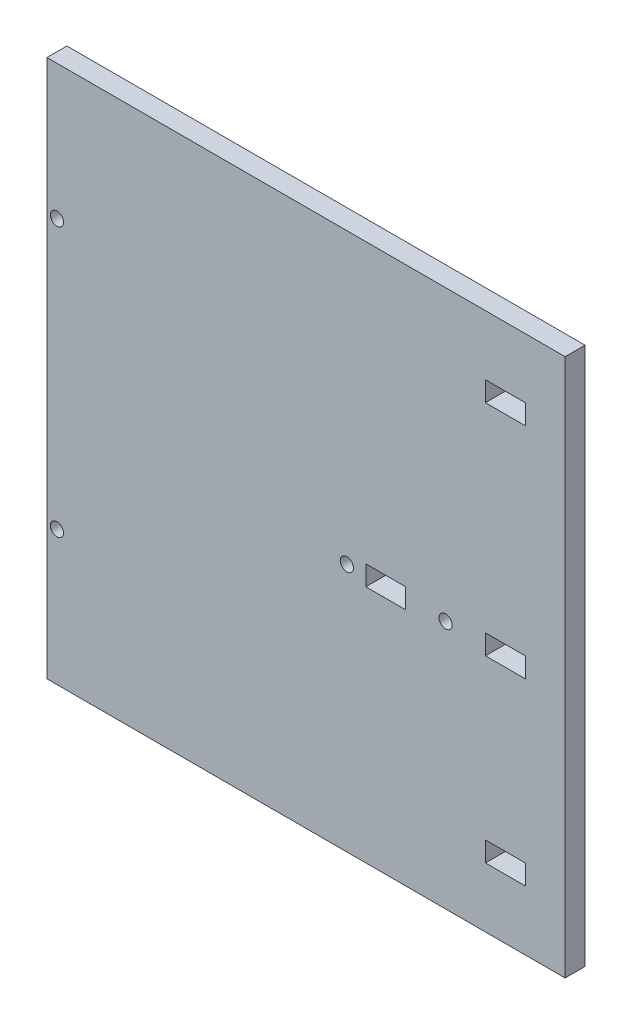
SolidWorks part; units mm, degrees
ref_plane "Front Plane" through (0, 0, 0) normal (0, 0, 1) x (1, 0, 0)
ref_plane "Top Plane" through (0, 0, 0) normal (0, 1, 0) x (1, 0, 0)
ref_plane "Right Plane" through (0, 0, 0) normal (1, 0, 0) x (0, 0, -1)
sketch "Sketch1" plane through (0, 0, 0) normal (0, 0, 1) x (1, 0, 0)
  line L1 (158.75, 155.575) -> (-6.35, 155.575)
  line L2 (158.75, 155.575) -> (158.75, -15.875)
  line L3 (158.75, -15.875) -> (-6.35, -15.875)
  line L4 (-6.35, 155.575) -> (-6.35, -15.875)
extrude "Boss-Extrude1" add sketch "Sketch1" along normal blind 6.35
sketch "Sketch2" plane through (0, 0, 6.35) normal (0, 0, 1) x (1, 0, 0)
  line L0 (122.7836, 66.675) -> (118.5164, 60.325) construction
  line L1 (146.05, 66.675) -> (133.35, 66.675)
  line L2 (146.05, 66.675) -> (146.05, 60.325)
  line L3 (146.05, 60.325) -> (133.35, 60.325)
  line L4 (133.35, 66.675) -> (133.35, 60.325)
  line L5 (107.95, 66.675) -> (95.25, 66.675)
  line L6 (107.95, 66.675) -> (107.95, 60.325)
  line L7 (107.95, 60.325) -> (95.25, 60.325)
  line L8 (95.25, 66.675) -> (95.25, 60.325)
  line L9 (122.7836, 60.325) -> (118.5164, 66.675) construction
  line L10 (91.3245, 60.325) -> (87.0573, 66.675) construction
  line L11 (91.3245, 66.675) -> (87.0573, 60.325) construction
  circle A0 centre (120.65, 63.5) radius 2.0955
  circle A1 centre (89.1909, 63.5) radius 2.0955
  dimension "D1" = 4.191
extrude "Cut-Extrude1" cut sketch "Sketch2" against normal through all
sketch "Sketch3" plane through (0, 0, 6.35) normal (0, 0, 1) x (1, 0, 0)
  line L0 (158.75, -15.875) -> (158.75, 155.575) construction
  line L1 (146.05, 9.525) -> (133.35, 9.525)
  line L2 (146.05, 9.525) -> (146.05, 3.175)
  line L3 (146.05, 3.175) -> (133.35, 3.175)
  line L4 (133.35, 9.525) -> (133.35, 3.175)
  line L5 (-6.35, -15.875) -> (158.75, -15.875) construction
  line L6 (158.75, 69.85) -> (109.7685, 69.85) construction
  line L7 (133.35, 130.175) -> (133.35, 136.525)
  line L8 (146.05, 136.525) -> (133.35, 136.525)
  line L9 (146.05, 130.175) -> (146.05, 136.525)
  line L10 (146.05, 130.175) -> (133.35, 130.175)
  dimension "D1" = 12.7
  dimension "D2" = 12.7
  dimension "D3" = 6.35
  dimension "D4" = 19.05
extrude "Cut-Extrude2" cut sketch "Sketch3" against normal through all
sketch "Sketch4" plane through (0, 0, 0) normal (0, 0, -1) x (-1, 0, 0)
  line L0 (0, 114.808) -> (6.35, 110.617) construction
  line L1 (6.35, 155.575) -> (6.35, -15.875) construction
  line L2 (0, 110.617) -> (6.35, 110.617) construction
  line L3 (0, 110.617) -> (6.35, 114.808) construction
  line L4 (0, 114.808) -> (6.35, 114.808) construction
  line L5 (0, 24.892) -> (6.35, 29.083) construction
  line L6 (0, 29.083) -> (6.35, 24.892) construction
  line L7 (0, 24.892) -> (6.35, 24.892) construction
  circle A0 centre (3.175, 26.9875) radius 2.0955
  circle A1 centre (3.175, 112.7125) radius 2.0955
  dimension "D1" = 4.191
extrude "Cut-Extrude3" cut sketch "Sketch4" against normal through all
